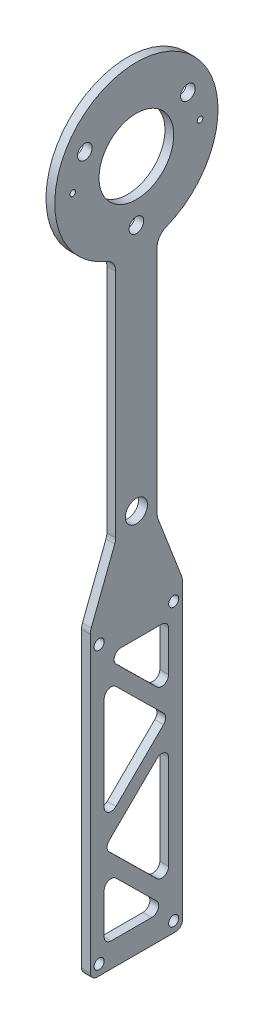
SolidWorks part; units mm, degrees
material "1060 Alloy"
ref_plane "Front Plane" through (0, 0, 0) normal (0, 0, 1) x (1, 0, 0)
ref_plane "Top Plane" through (0, 0, 0) normal (0, 1, 0) x (1, 0, 0)
ref_plane "Right Plane" through (0, 0, 0) normal (1, 0, 0) x (0, 0, -1)
sketch "Sketch1" plane through (0, 0, 0) normal (1, 0, 0) x (0, 0, -1)
  line L0 (-13.4747, 0) -> (13.4747, 0) construction
  line L1 (0, 0) -> (0, 35) construction
  line L2 (-13.4747, 0) -> (0, 35) construction
  line L3 (0, 35) -> (13.4747, 0) construction
  line L4 (13.4747, 0) -> (-13.4747, 0) construction
  line L5 (20.7574, -5) -> (-20.7574, -5)
  line L6 (-20.7574, -5) -> (0, 48.9165)
  line L7 (0, 48.9165) -> (20.7574, -5)
  line L8 (0, 35) -> (0, 146) construction
  line L9 (0, 35) -> (0, 146) construction
  line L12 (-7.5, 35) -> (-7.5, 146)
  line L13 (7.5, 35) -> (7.5, 146)
  line L14 (-7.5, 35) -> (-7.5, 29.4356)
  line L15 (7.5, 35) -> (7.5, 29.4356)
  line L16 (-13.4747, 0) -> (13.4747, 0) construction
  line L17 (-13.4747, 0) -> (-13.4747, -100) construction
  line L18 (13.4747, 0) -> (13.4747, -100) construction
  line L19 (-13.4747, -100) -> (13.4747, -100) construction
  line L20 (-20.7574, -5) -> (20.7574, -5)
  line L21 (-20.7574, -5) -> (-20.7574, -103.81)
  line L22 (20.7574, -5) -> (20.7574, -103.81)
  line L23 (-20.7574, -103.81) -> (20.7574, -103.81)
  circle A0 centre (-13.4747, 0) radius 1.8288
  circle A1 centre (0, 35) radius 4
  circle A2 centre (13.4747, 0) radius 1.8288
  circle A3 centre (0, 146) radius 3 construction
  arc A6 (-7.5, 35) -> (7.5, 35) centre (0, 35) ccw
  arc A7 (7.5, 146) -> (-7.5, 146) centre (0, 146) ccw
  circle A8 centre (-13.4747, -100) radius 1.8288
  circle A9 centre (13.4747, -100) radius 1.8288
  circle A10 centre (0, 146) radius 21.5 construction
  circle A11 centre (0, 124.5) radius 2.65
  circle A12 centre (18.6195, 156.75) radius 2.65
  circle A13 centre (-18.6195, 156.75) radius 2.65
  arc A14 (0, 124.5) -> (18.6195, 156.75) centre (0, 146) ccw construction
  arc A15 (0, 124.5) -> (-18.6195, 156.75) centre (0, 146) cw construction
  arc A16 (18.6195, 156.75) -> (-18.6195, 156.75) centre (0, 146) ccw construction
  circle A17 centre (0, 146) radius 13.5
  circle A18 centre (0, 146) radius 29.5
  point P4 (0, 0)
  point P14 (0, 90.5)
  point P34 (0, 146)
  dimension "D3" = 3.6576
  dimension "D4" = 8
  dimension "D7" = 6
  dimension "D11" = 43
  dimension "D12" = 5.3
  dimension "D13" = 27
  dimension "D14" = 59
  dimension "D1" = 26.9494
  dimension "D5" = 111
  dimension "D6" = 15
  dimension "D8" = 100
  dimension "D9" = 3.81
  dimension "D10" = 35
  dimension "D2" = 5
extrude "Boss-Extrude1" add sketch "Sketch1" along normal blind 3.175 contours L13 A18 L12 A17 A11 A12 A13 | L12 A18 L13 A17 | A18 L12 A6 L6 L7 L13 | L6 A6 L7 A1 | A6 L6 L5 L7 A2 A0 | A6 L14 L6 | A6 L7 L15 | L21 L23 L22 L5 A9 A8 region at (0, -54.1702, 0) region at (0, 9.5725, 0) region at (0, 31.6598, -7.2402) region at (0, 31.6598, 7.2402) region at (0, 27.7524, 0) region at (0, 77.9388, 0) region at (0, 116.7364, 0) region at (0, 126.1222, -8.3276)
sketch "Sketch2" plane through (3.175, 0, 0) normal (1, 0, 0) x (0, 0, -1)
  line L0 (-11.645, -5) -> (11.645, -5) construction
  line L1 (-11.645, -95) -> (11.645, -95) construction
  line L2 (11.645, -95) -> (11.645, -5) construction
  line L3 (-11.645, -95) -> (-11.645, -5) construction
  line L6 (11.645, -38.5118) -> (-11.645, -61.4882) construction
  line L7 (11.645, -5) -> (-11.645, -5)
  line L8 (-11.645, -5) -> (11.645, -27.9764)
  line L9 (11.645, -27.9764) -> (11.645, -5)
  line L10 (-11.645, -12.0236) -> (11.645, -35)
  line L11 (11.645, -35) -> (-11.645, -57.9764)
  line L12 (-11.645, -57.9764) -> (-11.645, -35)
  line L13 (-11.645, -35) -> (-11.645, -12.0236)
  line L14 (-11.645, -72.0236) -> (-11.645, -95)
  line L15 (-11.645, -95) -> (11.645, -95)
  line L16 (11.645, -95) -> (-11.645, -72.0236)
  line L17 (11.645, -42.0236) -> (11.645, -65)
  line L18 (11.645, -65) -> (11.645, -87.9764)
  line L19 (11.645, -87.9764) -> (-11.645, -65)
  line L20 (-11.645, -65) -> (11.645, -42.0236)
  line L21 (16.645, -1056.0877) -> (16.645, 48943.9123) construction
  line L22 (-16.645, -1060.2922) -> (-16.645, 48939.7078) construction
  line L23 (16.645, 29.4356) -> (-16.645, 29.4356) construction
  line L24 (-20.7574, -103.81) -> (-16.645, -103.81)
  line L25 (-20.7574, -103.81) -> (-20.7574, 29.4356)
  line L26 (-16.645, -103.81) -> (-16.645, 29.4356)
  line L27 (-20.7574, 29.4356) -> (-16.645, 29.4356)
  line L28 (-20.7574, -103.81) -> (20.7574, -103.81) construction
  line L29 (20.7574, -103.81) -> (16.645, -103.81)
  line L30 (20.7574, -103.81) -> (20.7574, 29.4356)
  line L31 (16.645, -103.81) -> (16.645, 29.4356)
  line L32 (20.7574, 29.4356) -> (16.645, 29.4356)
  circle A0 centre (13.4747, 0) radius 1.8288 construction
  circle A1 centre (13.4747, -100) radius 1.8288 construction
  point P6 (11.645, -50)
  point P10 (0, 29.4356)
  point P21 (0, -50)
  dimension "D1" = 33.29
  dimension "D2" = 5
  dimension "D3" = 5
  dimension "D4" = 5
  dimension "D5" = 5
  dimension "D6" = 2.5
  dimension "D8" = 5
  dimension "D7" = 2
extrude "Cut-Extrude1" cut sketch "Sketch2" against normal up to next
fillet "Fillet3" radius 2.5 14 edges at (1.5875, -57.9764, 11.645) (1.5875, -35, -11.645) (1.5875, -95, -11.645) (1.5875, -72.0236, 11.645) (1.5875, -95, 11.645) (1.5875, -27.9764, -11.645) (1.5875, -5, -11.645) (1.5875, -12.0236, 11.645) (1.5875, -5, 11.645) (1.5875, -87.9764, -11.645) (1.5875, -42.0236, -11.645) (1.5875, -65, 11.645) (1.5875, -103.81, -16.645) (1.5875, -103.81, 16.645)
fillet "Fillet4" radius 5 6 edges at (1.5875, 29.4356, -7.5) (1.5875, 29.4356, 7.5) (1.5875, 5.6818, 16.645) (1.5875, 5.6818, -16.645) (1.5875, 117.4693, -7.5) (1.5875, 117.4693, 7.5)
hole_wizard "M2.5x0.45 Tapped Hole1" positions "Sketch3" profile "Sketch4" tap size "M2.5x0.45" standard "ANSI Metric" end condition up to next
sketch "Sketch3" plane through (3.175, 0, 0) normal (1, 0, 0) x (0, 0, -1)
  line L0 (0, 124.5) -> (0, 146) construction
  line L2 (0, 146) -> (50000, 146) construction
  circle A0 centre (0, 146) radius 23.015 construction
  point P15 (-23.015, 146)
  point P17 (23.015, 146)
  dimension "D1" = 46.03
sketch "Sketch4" plane through (3.175, 146, -23.015) normal (0, 1, 0) x (0, 0, -1)
  line L0 (0, 0) -> (0, 3.175)
  line L1 (0, 3.175) -> (1.025, 3.175)
  line L2 (1.025, 3.175) -> (1.025, 0)
  line L5 (1.025, 0) -> (0, 0)
  line L11 (0, -6.35) -> (0, 107.95) construction
  dimension "Thru Tap Drill Dia." = 2.05
  dimension "Thru Tap Drill Depth" = 3.175
cosmetic thread "Hole Thread1" parameters "D2"=2.5
cosmetic thread "Hole Thread2" parameters "D2"=2.5
